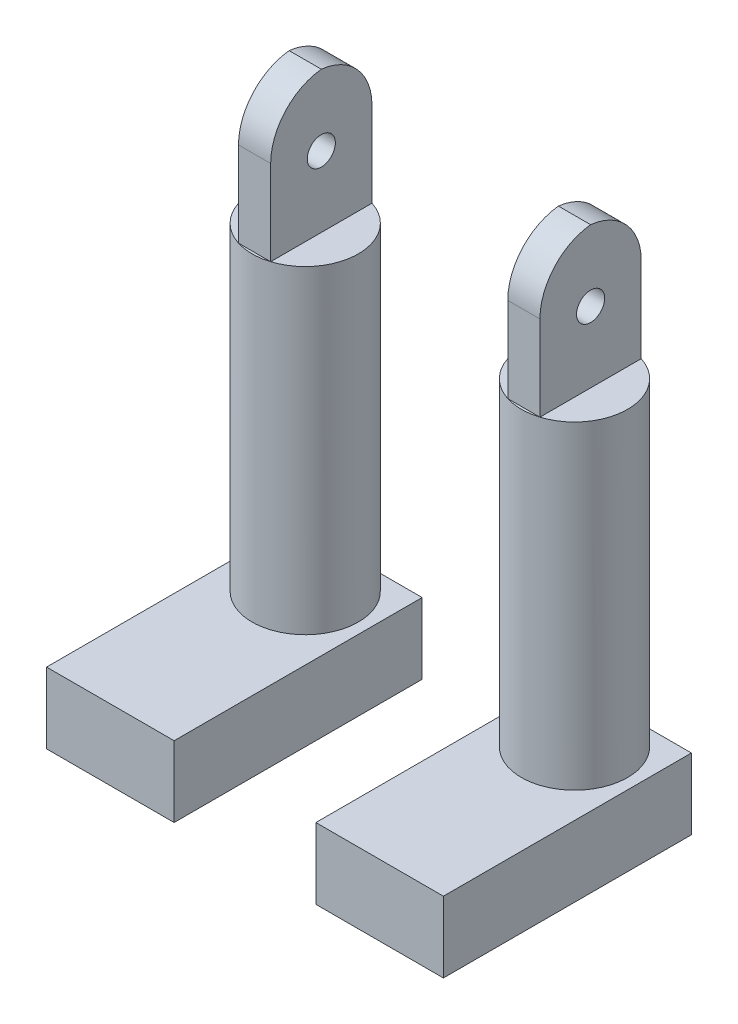
SolidWorks part; units mm, degrees
ref_plane "Front Plane" through (0, 0, 0) normal (0, 0, 1) x (1, 0, 0)
ref_plane "Top Plane" through (0, 0, 0) normal (0, 1, 0) x (1, 0, 0)
ref_plane "Right Plane" through (0, 0, 0) normal (1, 0, 0) x (0, 0, -1)
sketch "Sketch1" plane through (0, 0, 0) normal (0, 1, 0) x (1, 0, 0)
  line L0 (-540, 0) -> (-160, 0) construction
  line L2 (-630, -175) -> (-450, -175)
  line L3 (-630, -175) -> (-630, 175)
  line L4 (-630, 175) -> (-450, 175)
  line L5 (-450, -175) -> (-450, 175)
  line L6 (-630, -175) -> (-450, 175) construction
  line L7 (-630, 175) -> (-450, -175) construction
  line L8 (-250, -175) -> (-70, -175)
  line L9 (-250, -175) -> (-250, 175)
  line L10 (-250, 175) -> (-70, 175)
  line L11 (-70, -175) -> (-70, 175)
  line L12 (-250, -175) -> (-70, 175) construction
  line L13 (-250, 175) -> (-70, -175) construction
  dimension "D1" = 180
  dimension "D2" = 180
  dimension "D3" = 350
  dimension "D4" = 350
  dimension "D5" = 200
extrude "Boss-Extrude1" add sketch "Sketch1" along normal blind 100
sketch "Sketch2" plane through (0, 100, 0) normal (0, 1, 0) x (1, 0, 0)
  line L0 (-540, 175) -> (-540, -175) construction
  line L1 (-450, 175) -> (-630, 175) construction
  line L2 (-630, -175) -> (-450, -175) construction
  line L3 (-160, 175) -> (-160, -175) construction
  line L4 (-70, 175) -> (-250, 175) construction
  line L5 (-250, -175) -> (-70, -175) construction
  circle A0 centre (-540, 100) radius 75
  circle A1 centre (-160, 100) radius 75
  dimension "D1" = 150
  dimension "D2" = 150
  dimension "D3" = 75
  dimension "D4" = 75
extrude "Boss-Extrude2" add sketch "Sketch2" along normal blind 450
sketch "Sketch3" plane through (0, 550, 0) normal (0, 1, 0) x (1, 0, 0)
  line L1 (-562.7097, 28.5208) -> (-517.2903, 28.5208)
  line L2 (-562.7097, 28.5208) -> (-562.7097, 171.4792)
  line L3 (-562.7097, 171.4792) -> (-517.2903, 171.4792)
  line L4 (-517.2903, 28.5208) -> (-517.2903, 171.4792)
  line L5 (-562.7097, 28.5208) -> (-517.2903, 171.4792) construction
  line L6 (-562.7097, 171.4792) -> (-517.2903, 28.5208) construction
  line L7 (-182.7097, 28.5208) -> (-137.2903, 28.5208)
  line L8 (-182.7097, 28.5208) -> (-182.7097, 171.4792)
  line L9 (-182.7097, 171.4792) -> (-137.2903, 171.4792)
  line L10 (-137.2903, 28.5208) -> (-137.2903, 171.4792)
  line L11 (-182.7097, 28.5208) -> (-137.2903, 171.4792) construction
  line L12 (-182.7097, 171.4792) -> (-137.2903, 28.5208) construction
  circle A0 centre (-540, 100) radius 75 construction
  circle A1 centre (-160, 100) radius 75 construction
  point P0 (-540, 100)
  point P8 (-160, 100)
extrude "Boss-Extrude3" add sketch "Sketch3" along normal blind 200
fillet "Fillet1" radius 80 2 edges at (-540, 750, -171.4792) (-540, 750, -28.5208)
fillet "Fillet2" radius 80 2 edges at (-160, 750, -171.4792) (-160, 750, -28.5208)
sketch "Sketch4" plane through (-137.2903, 0, 0) normal (1, 0, 0) x (0, 0, -1)
  line L0 (100, 749.5449) -> (100, 550) construction
  line L1 (28.5208, 550) -> (171.4792, 550) construction
  circle A1 centre (100, 649.7725) radius 19.8124
extrude "Cut-Extrude1" cut sketch "Sketch4" against normal blind 579
